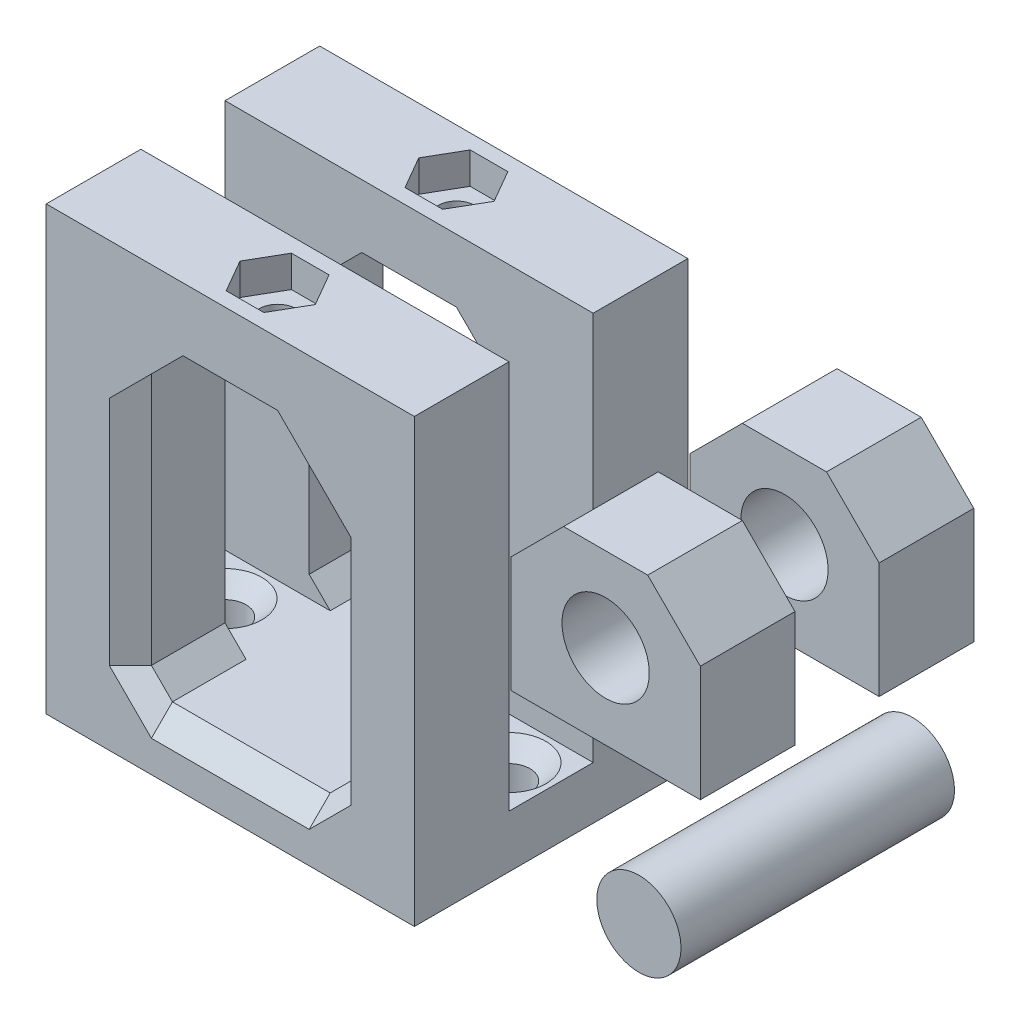
SolidWorks part; units mm, degrees
note: The reader was unsure of these and kept them because the rebuilt part matched: shared geometry of "Sketch1<3>", "Sketch1<4>", "Sketch1<5>".
ref_plane "Front Plane" through (0, 0, 0) normal (0, 0, 1) x (1, 0, 0)
ref_plane "Top Plane" through (0, 0, 0) normal (0, 1, 0) x (1, 0, 0)
ref_plane "Right Plane" through (0, 0, 0) normal (1, 0, 0) x (0, 0, -1)
sketch "Sketch1" plane through (0, 0, 0) normal (0, 1, 0) x (1, 0, 0)
  line L0 (0, 13) -> (35, 13) construction
  line L1 (0, 0) -> (35, 0)
  line L2 (0, 0) -> (0, 26)
  line L3 (0, 26) -> (35, 26)
  line L4 (35, 0) -> (35, 26)
  line L5 (6.5, 16.5) -> (28.5, 16.5) construction
  line L6 (6.5, 16.5) -> (6.5, 9.5) construction
  line L7 (6.5, 9.5) -> (28.5, 9.5) construction
  line L8 (28.5, 16.5) -> (28.5, 9.5) construction
  line L9 (0, 0) -> (35, 0)
  line L10 (0, 0) -> (0, 9)
  line L11 (0, 9) -> (35, 9)
  line L12 (35, 0) -> (35, 9)
  line L13 (0, 17) -> (35, 17)
  line L14 (17.5, 26) -> (17.5, 0) construction
  line L15 (0, 26) -> (0, 17) construction
  line L16 (0, 0) -> (0, 9) construction
  line L17 (17.5, 26) -> (17.5, 17) construction
  line L18 (21.0796, 4.5) -> (19.2898, 1.4)
  line L19 (15.7102, 18.4) -> (19.2898, 18.4)
  line L20 (19.2898, 18.4) -> (21.0796, 21.5)
  line L21 (21.0796, 21.5) -> (19.2898, 24.6)
  line L22 (19.2898, 24.6) -> (15.7102, 24.6)
  line L23 (15.7102, 24.6) -> (13.9204, 21.5)
  line L24 (13.9204, 21.5) -> (15.7102, 18.4)
  line L25 (19.2898, 7.6) -> (21.0796, 4.5)
  line L26 (15.7102, 7.6) -> (19.2898, 7.6)
  line L27 (13.9204, 4.5) -> (15.7102, 7.6)
  line L28 (15.7102, 1.4) -> (13.9204, 4.5)
  line L29 (19.2898, 1.4) -> (15.7102, 1.4)
  circle A0 centre (4, 13) radius 2
  circle A1 centre (31, 13) radius 2
  circle A2 centre (17.5, 21.5) radius 3.1 construction
  circle A3 centre (17.5, 21.5) radius 1.75
  circle A4 centre (17.5, 4.5) radius 1.75
  point P9 (0, 13)
  point P10 (6.5, 13)
  point P11 (17.5, 9.5)
  point P12 (17.5, 0)
  point P45 (2.497, 13)
  dimension "D4" = 6.2
  dimension "D6" = 3.5
  dimension "D8" = 4
  dimension "D9" = 4
  dimension "D1" = 35
  dimension "D2" = 7
  dimension "D3" = 22
  dimension "D5" = 8
  dimension "D7" = 9
extrude "Boss-Extrude1" add sketch "Sketch1" along normal blind 5 contours L2 L13 L4 L3 L24 L23 L22 L21 L20 L19 | L13 L2 L11 L4 A0 A1 | L11 L2 L1 L4 L18 L29 L28 L27 L26 L25 | L23 L24 L19 L20 L21 L22 A3 | A4 | L29 L18 L25 L26 L27 L28 A4 | A3
extrude "Boss-Extrude2" add sketch "Sketch1<3>" along normal blind 42 contours L2 L13 L4 L3 L24 L23 L22 L21 L20 L19 | L11 L2 L1 L4 L18 L29 L28 L27 L26 L25 | L23 L24 L19 L20 L21 L22 A3 | L29 L18 L25 L26 L27 L28 A4 | A4 | A3
sketch "Sketch1<3>" plane through (0, 0, 0) normal (0, 1, 0) x (1, 0, 0) same geometry as "Sketch1"
sketch "Sketch2" plane through (0, 0, 0) normal (0, 0, 1) x (1, 0, 0)
  line L0 (17.5, 0) -> (17.5, 28) construction
  line L1 (0, 0) -> (35, 0) construction
  line L3 (8, 36) -> (27, 36)
  line L4 (8, 36) -> (8, 5)
  line L5 (8, 5) -> (27, 5)
  line L6 (27, 36) -> (27, 5)
  line L7 (0, 42) -> (0, 0) construction
  circle A0 centre (17.5, 28) radius 11 construction
  circle A1 centre (17.5, 28) radius 4.15
  point P14 (17.5, 5)
  point P15 (0, 0)
  point P16 (0, 0)
  point P17 (0, 0)
  point P18 (0, 0)
  dimension "D1" = 22
  dimension "D3" = 8.3
  dimension "D2" = 28
  dimension "D4" = 5
  dimension "D5" = 8
  dimension "D6" = 8
extrude "Cut-Extrude1" cut sketch "Sketch1<4>" against normal blind 3 from surface at 42 contours L23 L24 L19 L20 L21 L22 A3 | L29 L18 L25 L26 L27 L28 A4 | A4 | A3 starting at face at (17.5, 42, -4.5)
sketch "Sketch1<4>" plane through (0, 0, 0) normal (0, 1, 0) x (1, 0, 0) same geometry as "Sketch1"
extrude "Cut-Extrude2" cut sketch "Sketch1<5>" against normal up to surface (37 mm away) from surface at 42 contours A3 | A4 up to face at (4, 5, -11) starting at face at (17.5, 42, -21.5)
sketch "Sketch1<5>" plane through (0, 0, 0) normal (0, 1, 0) x (1, 0, 0) same geometry as "Sketch1"
extrude "Cut-Extrude3" cut sketch "Sketch2" against normal through all and the other way through all contours A1 | L6 L3 L4 L5 A1
chamfer "Chamfer1" distance 5 angle 45 4 edges at (8, 36, -21.5) (27, 36, -21.5) (27, 36, -4.5) (8, 36, -4.5)
sketch "Sketch3" plane through (0, 0, -26) normal (0, 0, -1) x (-1, 0, 0)
  line L0 (-62.1873, 35.0286) -> (-57.1873, 40.0286)
  line L1 (-62.1873, 40.0286) -> (-44.1873, 40.0286)
  line L2 (-62.1873, 40.0286) -> (-62.1873, 24.0286)
  line L3 (-62.1873, 24.0286) -> (-44.1873, 24.0286)
  line L4 (-44.1873, 40.0286) -> (-44.1873, 24.0286)
  line L5 (-49.1873, 40.0286) -> (-44.1873, 35.0286)
  circle A0 centre (-53.1873, 32.0286) radius 4.15
  circle A1 centre (-17.5, 28) radius 4.15 construction
  point P10 (-53.1873, 40.0286)
  point P13 (0, 0)
  point P14 (0, 0)
  dimension "D4" = 8
  dimension "D5" = 16
  dimension "D1" = 5
  dimension "D2" = 45
  dimension "D3" = 18
extrude "Boss-Extrude3" add sketch "Sketch3" against normal up to surface (9 mm away) separate body contours L5 L1 L0 L2 L3 L4 A0 up to face at (17.5, 23.8, -17)
ref_plane "Plane2" through (0, 0, -13) normal (0, 0, -1) x (-1, 0, 0)
mirror "Mirror2" about plane through (0, 0, -13) normal (0, 0, -1) of bodies 106
chamfer "Chamfer2" distance 1.5 angle 45 2 edges at (31, 5, -11) (4, 5, -11)
sketch "Sketch4" plane through (0, 0, -26) normal (0, 0, -1) x (-1, 0, 0)
  circle A0 centre (-56.3499, 10.9019) radius 4
  point P2 (0, 0)
  dimension "D1" = 8
extrude "Boss-Extrude4" add sketch "Sketch4" against normal up to surface (26 mm away) separate body up to face at (17.5, 21, 0)
chamfer "Chamfer3" distance 2 angle 45 10 edges at (8, 18, 0) (27, 18, 0) (8, 5, -4.5) (17.5, 5, 0) (27, 5, -4.5) (8, 18, -26) (27, 18, -26) (8, 5, -21.5) (17.5, 5, -26) (27, 5, -21.5)
